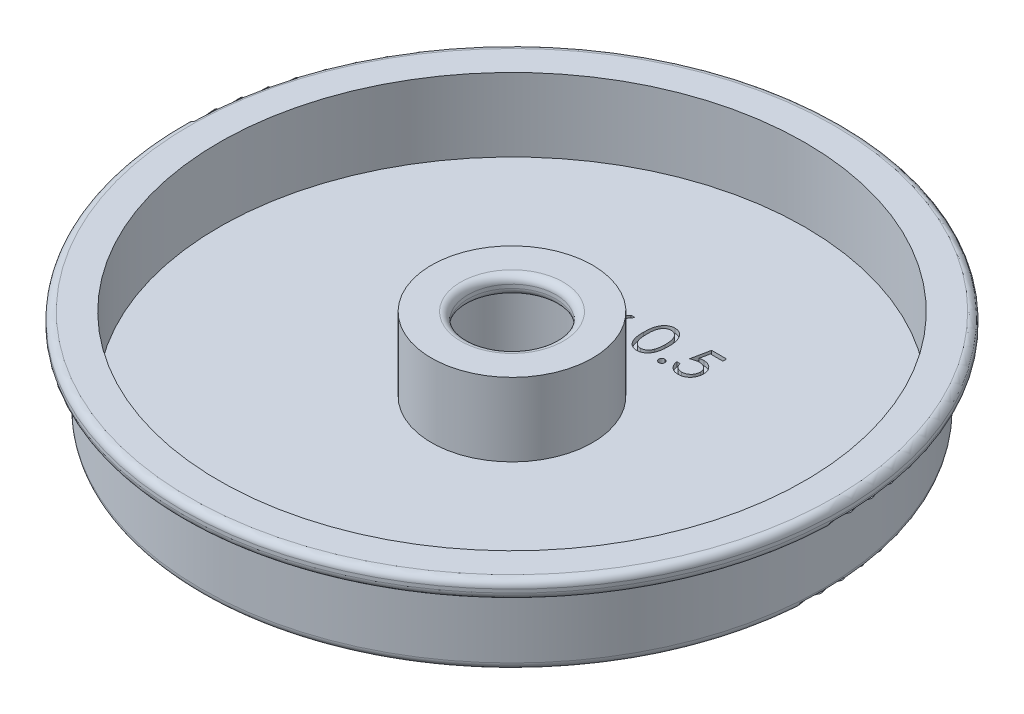
SolidWorks part; units mm, degrees
ref_plane "Front Plane" through (0, 0, 0) normal (0, 0, 1) x (1, 0, 0)
ref_plane "Top Plane" through (0, 0, 0) normal (0, 1, 0) x (1, 0, 0)
ref_plane "Right Plane" through (0, 0, 0) normal (1, 0, 0) x (0, 0, -1)
sketch "Sketch1" plane through (0, 0, 0) normal (0, 0, 1) x (1, 0, 0)
  line L0 (0, 0) -> (0, 11.1543)
  line L3 (13.97, 15.9118) -> (13.97, 3.2118)
  line L4 (13.97, 3.2118) -> (50.8, 3.2118)
  line L5 (50.8, 3.2118) -> (50.8, 15.9118)
  line L8 (52.705, 0.0368) -> (12.065, 0.0368)
  line L9 (53.975, 1.3068) -> (53.975, 11.5037)
  line L10 (55.245, 12.7737) -> (55.88, 12.7737)
  line L11 (57.15, 14.0437) -> (57.15, 14.6418)
  line L12 (50.8, 15.9118) -> (55.88, 15.9118)
  line L13 (13.97, 15.9118) -> (8.89, 15.9118)
  line L14 (7.62, 14.6418) -> (7.62, 14.0068)
  line L15 (10.795, 1.3068) -> (10.795, 11.4668)
  line L16 (9.525, 12.7368) -> (8.89, 12.7368)
  arc A0 (55.88, 15.9118) -> (57.15, 14.6418) centre (55.88, 14.6418) cw
  arc A1 (57.15, 14.0437) -> (55.88, 12.7737) centre (55.88, 14.0437) cw
  arc A2 (55.245, 12.7737) -> (53.975, 11.5037) centre (55.245, 11.5037) ccw
  arc A3 (53.975, 1.3068) -> (52.705, 0.0368) centre (52.705, 1.3068) cw
  arc A4 (12.065, 0.0368) -> (10.795, 1.3068) centre (12.065, 1.3068) cw
  arc A5 (10.795, 11.4668) -> (9.525, 12.7368) centre (9.525, 11.4668) ccw
  arc A6 (8.89, 12.7368) -> (7.62, 14.0068) centre (8.89, 14.0068) cw
  arc A7 (7.62, 14.6418) -> (8.89, 15.9118) centre (8.89, 14.6418) cw
  dimension "D10" = 1.27
  dimension "D1" = 3.175
  dimension "D2" = 6.35
  dimension "D3" = 3.175
  dimension "D4" = 6.35
  dimension "D5" = 3.175
  dimension "D6" = 13.97
  dimension "D7" = 50.8
  dimension "D8" = 3.1382
  dimension "D9" = 3.175
  dimension "D11" = 12.7
  dimension "D12" = 12.7
revolve "Revolve2" add sketch "Sketch1" angle 360 about L0 region at (13.4499, 9.5618, 0)
sketch "Sketch2" plane through (0, 3.2118, 0) normal (0, 1, 0) x (1, 0, 0)
  text T0 "4 x 0.5" font "Century Gothic" height in points 24
extrude "Cut-Extrude1" cut sketch "Sketch2" against normal blind 0.7937
